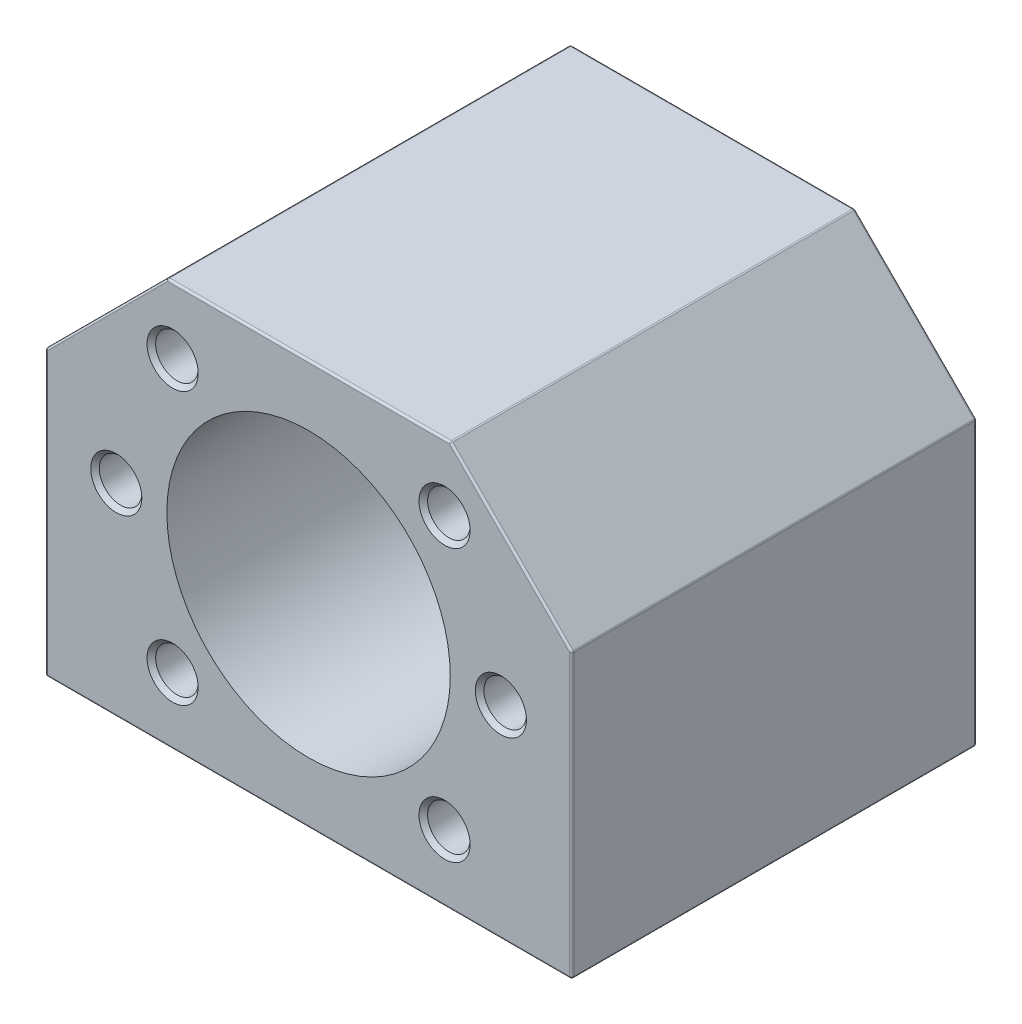
SolidWorks part; units mm, degrees
ref_plane "Plan de face" through (0, 0, 0) normal (0, 0, 1) x (1, 0, 0)
ref_plane "Plan de dessus" through (0, 0, 0) normal (0, 1, 0) x (1, 0, 0)
ref_plane "Plan de droite" through (0, 0, 0) normal (1, 0, 0) x (0, 0, -1)
sketch "Esquisse1" plane through (0, 0, 0) normal (0, 0, 1) x (1, 0, 0)
  line L1 (0, 0) -> (52, 0)
  line L2 (0, 0) -> (0, 40)
  line L3 (0, 40) -> (52, 40)
  line L4 (52, 0) -> (52, 40)
  circle A0 centre (26, 20) radius 14
  point P7 (26, 0)
  point P8 (0, 0)
  point P9 (0, 20)
  dimension "D1" = 52
  dimension "D3" = 28
  dimension "D2" = 40
extrude "Boss.-Extru.1" add sketch "Esquisse1" along normal blind 40
chamfer "Chanfrein1" distance 12 angle 45 2 edges at (0, 40, 20) (52, 40, 20)
fillet "Congé1" radius 0.2 19 edges at (52, 14, 0) (46, 34, 0) (26, 40, 0) (6, 34, 0) (0, 14, 0) (52, 28, 20) (40, 40, 20) (12, 40, 20) (0, 28, 20) (6, 34, 40) (26, 40, 40) (46, 34, 40) (52, 14, 40) (52, 0, 20) (26, 0, 0) (0, 14, 40) (0, 0, 20) (26, 0, 40) (40, 20, 0)
sketch "Эскиз1" plane through (0, 0, 0) normal (0, -1, 0) x (1, 0, 0)
  line L0 (0.2, 40) -> (51.8, 40) construction
  line L1 (6, 32) -> (46, 32) construction
  line L2 (6, 32) -> (6, 8) construction
  line L3 (6, 8) -> (46, 8) construction
  line L4 (46, 32) -> (46, 8) construction
  line L5 (51.8, 0) -> (0.2, 0) construction
  line L6 (26, 40) -> (26, 0) construction
  point P10 (26, 32)
  dimension "D1" = 24
  dimension "D2" = 40
  dimension "D3" = 8
hole_wizard "Отверстие обработанное метчиком M5x0.81" positions "Эскиз2" profile "Эскиз3" tap size "M5x0.8" standard "Ansi Metric"
sketch "Эскиз2" plane through (0, 0, 0) normal (0, -1, 0) x (-1, 0, 0)
  point P0 (-6, -32)
  point P3 (-46, -32)
  point P6 (-46, -8)
  point P9 (-6, -8)
sketch "Эскиз3" plane through (6, 0, 32) normal (1, 0, 0) x (0, 0, -1)
  line L0 (0, 0) -> (0, 15.2618)
  line L1 (0, 15.2618) -> (2.1, 14)
  line L2 (2.1, 14) -> (2.1, 0.425)
  line L3 (2.1, 0.425) -> (2.525, 0)
  line L5 (2.525, 0) -> (0, 0)
  line L6 (-2.1, 0.425) -> (-2.525, 0) construction
  line L10 (0, 15.2618) -> (-2.1, 14) construction
  line L11 (0, -6.35) -> (0, 107.95) construction
  dimension "Диаметр сверла" = 4.2
  dimension "Глубина сверла" = 14
  dimension "Диаметр передней зенковки" = 5.05
  dimension "Угол передней зенковки" = 90
  dimension "Угол заточки сверла" = 118
cosmetic thread "Отверстие резьбы1" parameters "D1"=10, "D2"=5
cosmetic thread "Отверстие резьбы2" parameters "D1"=10, "D2"=5
cosmetic thread "Отверстие резьбы3" parameters "D1"=10, "D2"=5
cosmetic thread "Отверстие резьбы4" parameters "D1"=10, "D2"=5
sketch "Эскиз4" plane through (0, 0, 40) normal (0, 0, 1) x (1, 0, 0)
  line L0 (6, 0) -> (46, 0) construction
  line L1 (26, 40) -> (26, 0) construction
  line L2 (12.0828, 40) -> (39.9172, 40) construction
  circle A0 centre (26, 20) radius 19 construction
  point P4 (7, 20)
  point P5 (45, 20)
  dimension "D1" = 38
  dimension "D2" = 20
hole_wizard "Отверстие обработанное метчиком M5x0.82" positions "Эскиз5" profile "Эскиз6" tap size "M5x0.8" standard "Ansi Metric"
sketch "Эскиз5" plane through (0, 0, 40) normal (0, 0, 1) x (1, 0, 0)
  point P0 (7, 20)
  point P3 (45, 20)
sketch "Эскиз6" plane through (7, 20, 40) normal (1, 0, 0) x (0, -1, 0)
  line L0 (0, 0) -> (0, 15.2618)
  line L1 (0, 15.2618) -> (2.1, 14)
  line L2 (2.1, 14) -> (2.1, 0.425)
  line L3 (2.1, 0.425) -> (2.525, 0)
  line L5 (2.525, 0) -> (0, 0)
  line L6 (-2.1, 0.425) -> (-2.525, 0) construction
  line L10 (0, 15.2618) -> (-2.1, 14) construction
  line L11 (0, -6.35) -> (0, 107.95) construction
  dimension "Диаметр сверла" = 4.2
  dimension "Глубина сверла" = 14
  dimension "Диаметр передней зенковки" = 5.05
  dimension "Угол передней зенковки" = 90
  dimension "Угол заточки сверла" = 118
cosmetic thread "Отверстие резьбы5" parameters "D1"=10, "D2"=5
cosmetic thread "Отверстие резьбы6" parameters "D1"=10, "D2"=5
ref_axis "Ось1" through (26, 20, 40) along (0, 0, 1)
pattern_circular "Круговой массив1" count 2 every 45 about axis through (26, 20, 40) along (0, 0, 1) of "Отверстие обработанное метчиком M5x0.82"
pattern_circular "Круговой массив2" count 2 every 315 about axis through (26, 20, 40) along (0, 0, 1) of "Отверстие обработанное метчиком M5x0.82"
